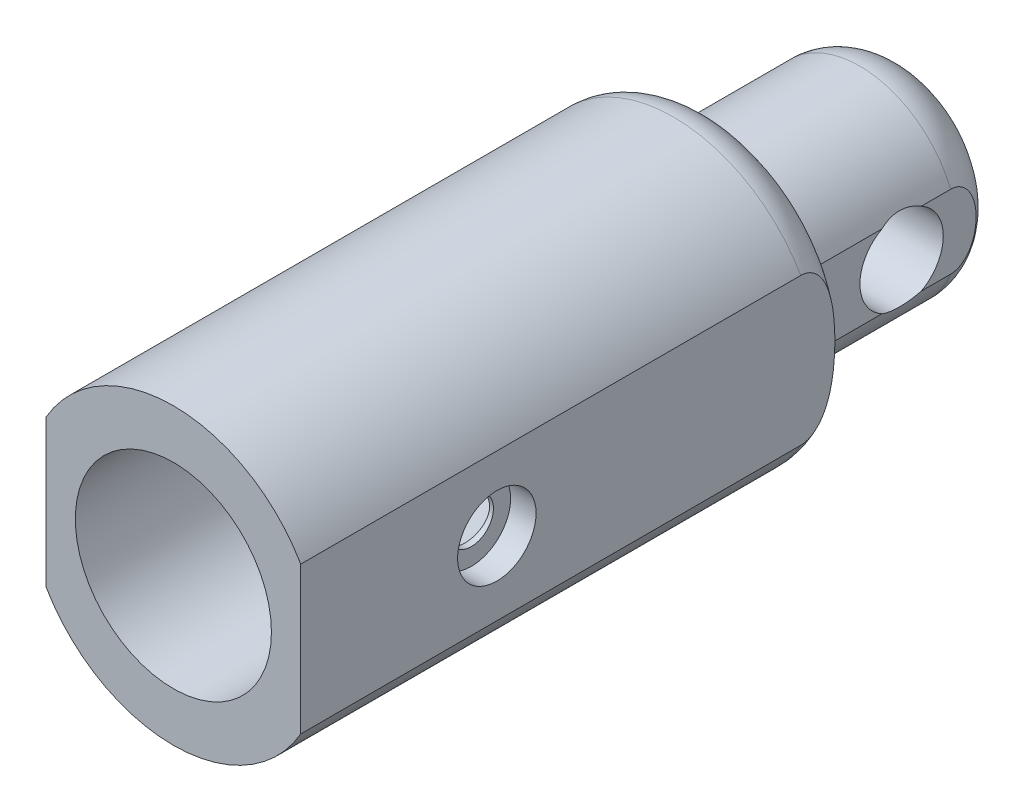
SolidWorks part; units mm, degrees
ref_plane "Front Plane" through (0, 0, 0) normal (0, 0, 1) x (1, 0, 0)
ref_plane "Top Plane" through (0, 0, 0) normal (0, 1, 0) x (1, 0, 0)
ref_plane "Right Plane" through (0, 0, 0) normal (1, 0, 0) x (0, 0, -1)
sketch "Sketch2" plane through (0, 0, 0) normal (0, 0, 1) x (1, 0, 0)
  line L0 (12.9904, 7.5) -> (12.9904, -7.5)
  line L1 (-12.9904, 7.5) -> (-12.9904, -7.5)
  circle A0 centre (0, 0) radius 10
  circle A1 centre (0, 0) radius 15
  dimension "D1" = 30
  dimension "D2" = 20
  dimension "D3" = 15
  dimension "D4" = 15
extrude "Boss-Extrude2" add sketch "Sketch2" against normal blind 55 contours A1 A0 | A0 region at (12.5935, 0, 0) region at (0, 0, 0)
sketch "Sketch6" plane through (0, 0, -55) normal (0, 0, -1) x (-1, 0, 0)
  line L0 (-9.2702, 3.75) -> (-9.2702, -3.75)
  line L1 (9.2702, 3.75) -> (9.2702, -3.75)
  circle A0 centre (0, 0) radius 10
  dimension "D1" = 20
  dimension "D2" = 7.5
  dimension "D3" = 7.5
extrude "Boss-Extrude4" add sketch "Sketch6" along normal blind 20 contours L1 A0 L0 region at (0, 0, -55)
sketch "Sketch7" plane through (0, 0, 0) normal (1, 0, 0) x (0, 0, -1)
  line L1 (75, -10) -> (55, -10)
  line L2 (75, -10) -> (55, -10)
  line L4 (65, 10) -> (65, -10) construction
  circle A0 centre (65, 0) radius 4.25
  dimension "D1" = 8.5
extrude "Cut-Extrude4" cut sketch "Sketch7" against normal through all and the other way through all contours A0
sketch "Sketch8" plane through (0, 0, -75) normal (0, 0, -1) x (-1, 0, 0)
  line L0 (0, 0) -> (0, 4.2724)
  line L1 (3.7, -2.1362) -> (3.7, 2.1362)
  line L2 (3.7, 2.1362) -> (0, 4.2724)
  line L3 (0, 4.2724) -> (-3.7, 2.1362)
  line L4 (-3.7, 2.1362) -> (-3.7, -2.1362)
  line L5 (-3.7, -2.1362) -> (0, -4.2724)
  line L6 (0, -4.2724) -> (3.7, -2.1362)
  circle A0 centre (0, 0) radius 3.7 construction
  circle A1 centre (0, 0) radius 2.25
  dimension "D1" = 7.4
  dimension "D2" = 4.5
extrude "Cut-Extrude5" cut sketch "Sketch8" against normal up to next contours A1 region at (-1.546, 1.546, -75)
extrude "Cut-Extrude6" cut sketch "Sketch8<3>" against normal blind 4 contours A1 L3 L4 L5 L6 L1 L2 region at (-1.7935, 3.1064, -75)
sketch "Sketch8<3>" plane through (0, 0, -75) normal (0, 0, -1) x (-1, 0, 0) same geometry as "Sketch8"
extrude "Cut-Extrude7" cut sketch "Sketch2<5>" against normal blind 50 contours A0 region at (0, 0, 0)
sketch "Sketch2<5>" plane through (0, 0, 0) normal (0, 0, 1) x (1, 0, 0) same geometry as "Sketch2"
fillet "Fillet1" radius 4 1 edges at (0, 15, -55)
fillet "Fillet3" radius 5 1 edges at (0, 10, -75)
sketch "Sketch9" plane through (-12.9904, 0, 0) normal (-1, 0, 0) x (0, 0, 1)
  line L0 (0, 0) -> (-20, 0) construction
  line L2 (-15.6699, 0) -> (-17.8349, 3.75)
  line L3 (-17.8349, 3.75) -> (-22.1651, 3.75)
  line L4 (-22.1651, 3.75) -> (-24.3301, 0)
  line L5 (-24.3301, 0) -> (-22.1651, -3.75)
  line L6 (-22.1651, -3.75) -> (-17.8349, -3.75)
  line L7 (-17.8349, -3.75) -> (-15.6699, 0)
  circle A0 centre (-20, 0) radius 3.75 construction
  dimension "D2" = 7.5
  dimension "D1" = 20
sketch "Sketch10" plane through (12.9904, 0, 0) normal (1, 0, 0) x (0, 0, -1)
  line L0 (0, 0) -> (20, 0) construction
hole_wizard "CBORE for M4 Cheese Head Screw1" positions "Sketch11" profile "Sketch12" counterbore size "M4" standard "AS" end condition through all
sketch "Sketch11" plane through (12.9904, 0, 0) normal (1, 0, 0) x (0, 0, -1)
  point P0 (20, 0)
sketch "Sketch12" plane through (12.9904, 0, -20) normal (0, 1, 0) x (0, 0, -1)
  line L0 (0, 0) -> (0, 25.9808)
  line L1 (0, 25.9808) -> (2.25, 25.9808)
  line L3 (2.25, 25.9808) -> (2.25, 2.6)
  line L4 (2.25, 2.6) -> (4, 2.6)
  line L5 (4, 2.6) -> (4, 0)
  line L7 (4, 0) -> (0, 0)
  line L11 (0, -6.35) -> (0, 107.95) construction
  dimension "Thru Hole Dia." = 4.5
  dimension "Thru Hole Depth" = 25.9808
  dimension "C'Bore Dia." = 8
  dimension "C'Bore Depth" = 2.6
extrude "Cut-Extrude8" cut sketch "Sketch9" against normal blind 1
